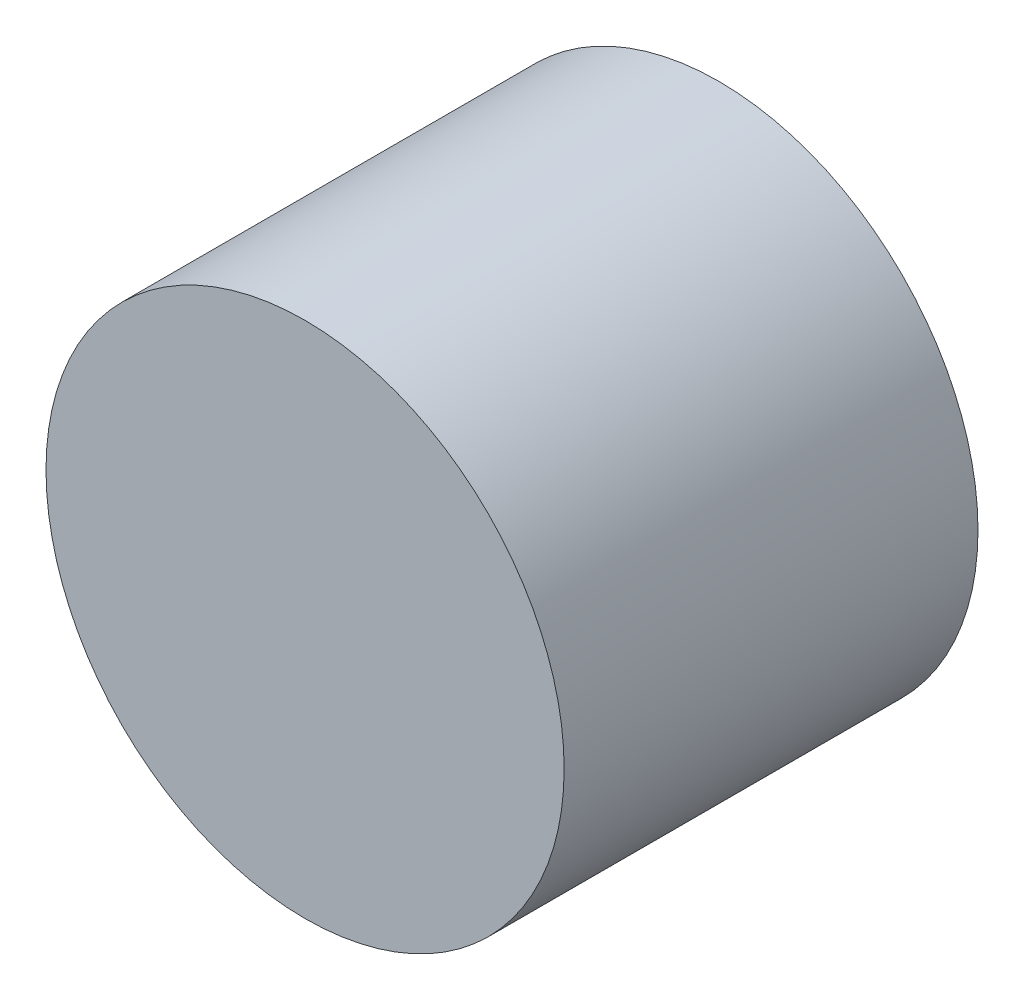
SolidWorks part; units mm, degrees
ref_plane "Front Plane" through (0, 0, 0) normal (0, 0, 1) x (1, 0, 0)
ref_plane "Top Plane" through (0, 0, 0) normal (0, 1, 0) x (1, 0, 0)
ref_plane "Right Plane" through (0, 0, 0) normal (1, 0, 0) x (0, 0, -1)
sketch "Sketch1" plane through (0, 0, 0) normal (0, 0, 1) x (1, 0, 0)
  circle A0 centre (0, 0) radius 15.9
  dimension "D1" = 31.8
extrude "Boss-Extrude1" add sketch "Sketch1" along normal blind 25.4
